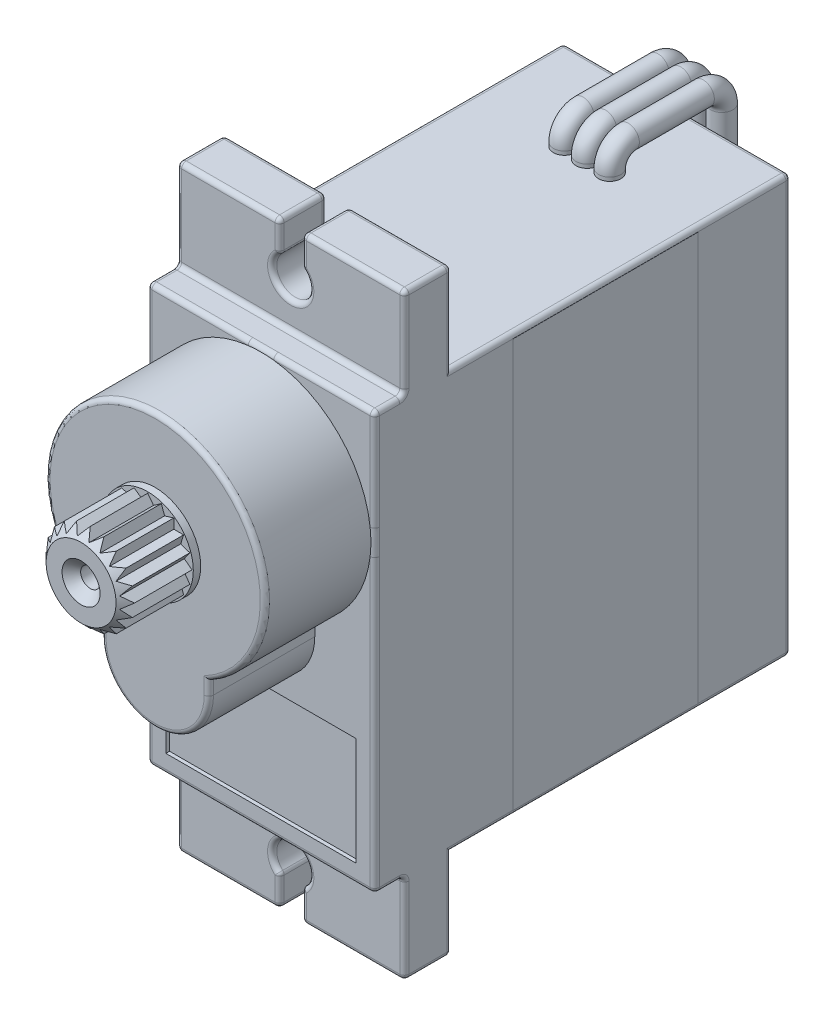
SolidWorks part; units mm, degrees
note: The reader was unsure of these and kept them because the rebuilt part matched: shared geometry of "Sketch1<3>", "Sketch3<3>", "Sketch8<3>".
ref_plane "Front Plane" through (0, 0, 0) normal (0, 0, 1) x (1, 0, 0)
ref_plane "Top Plane" through (0, 0, 0) normal (0, 1, 0) x (1, 0, 0)
ref_plane "Right Plane" through (0, 0, 0) normal (1, 0, 0) x (0, 0, -1)
sketch "Sketch1" plane through (0, 0, 0) normal (0, 0, 1) x (1, 0, 0)
  line L5 (-6.14, -16.41) -> (6.14, -16.41)
  line L6 (2.9, -5.93) -> (2.9, -5.1725)
  line L7 (-2.9, -5.93) -> (-2.9, -5.1725)
  line L8 (-6.14, -16.41) -> (-6.14, 6.14)
  line L9 (-6.14, 6.14) -> (6.14, 6.14)
  line L10 (6.14, -16.41) -> (6.14, 6.14)
  circle A0 centre (0, 0) radius 5.93
  arc A1 (-2.9, -5.93) -> (2.9, -5.93) centre (0, -5.93) ccw
  circle A2 centre (0, 0) radius 6.14 construction
  dimension "D3" = 11.86
  dimension "D4" = 5.8
  dimension "D6" = 12.28
  dimension "D7" = 22.55
ref_plane "Plane1" through (0, 0, -1.6) normal (0, 0, 1) x (1, 0, 0)
sketch "Sketch2" plane through (0, 0, -1.6) normal (0, 0, 1) x (1, 0, 0)
  line L1 (-6.14, 6.14) -> (6.14, 6.14)
  line L2 (-6.14, 6.14) -> (-6.14, 11)
  line L3 (-6.14, 11) -> (-0.6, 11)
  line L4 (6.14, 6.14) -> (6.14, 11)
  line L7 (0, 8.57) -> (0, 12.1069) construction
  line L8 (0.6, 9.37) -> (0.6, 11)
  line L9 (-0.6, 9.37) -> (-0.6, 11)
  line L10 (0.6, 11) -> (6.14, 11)
  line L11 (-0.6, 8.57) -> (-0.6, 12.1069) construction
  line L12 (0.6, 8.57) -> (0.6, 12.1069) construction
  line L13 (-6.14, -5.135) -> (6.14, -5.135) construction
  line L14 (0, -18.84) -> (0, -22.3769) construction
  line L15 (0.6, -21.27) -> (6.14, -21.27)
  line L16 (-0.6, -19.64) -> (-0.6, -21.27)
  line L17 (0.6, -19.64) -> (0.6, -21.27)
  line L18 (6.14, -16.41) -> (6.14, -21.27)
  line L19 (-6.14, -21.27) -> (-0.6, -21.27)
  line L20 (-6.14, -16.41) -> (-6.14, -21.27)
  line L21 (-6.14, -16.41) -> (6.14, -16.41)
  line L22 (-6.14, 6.14) -> (6.14, 6.14) construction
  line L23 (-6.14, -16.41) -> (-6.14, 6.14) construction
  line L24 (6.14, -16.41) -> (6.14, 6.14) construction
  arc A0 (-0.6, 9.37) -> (0.6, 9.37) centre (0, 8.57) ccw
  arc A1 (-0.6, -19.64) -> (0.6, -19.64) centre (0, -18.84) cw
  point P16 (6.14, 8.57)
  dimension "D2" = 0.6
  dimension "D4" = 2
  dimension "D1" = 4.86
  dimension "D3" = 0.6
extrude "Main Body" add sketch "Sketch1" against normal blind 22.46
extrude "Front Dial" add sketch "Sketch1<3>" along normal blind 5.72 contours L7 A1 L6 A0 | A0
sketch "Sketch1<3>" plane through (0, 0, 0) normal (0, 0, 1) x (1, 0, 0) same geometry as "Sketch1"
sketch "Sketch3" plane through (0, 0, 5.72) normal (0, 0, 1) x (1, 0, 0)
  line L0 (0, 0) -> (0, 2.39) construction
  line L1 (0, 0) -> (0.7386, 2.273) construction
  line L2 (0.7386, 2.273) -> (0.908, 1.782)
  line L3 (0.908, 1.782) -> (1.4048, 1.9336)
  line L4 (1.4048, 1.9336) -> (1.4142, 1.4142)
  line L5 (1.4142, 1.4142) -> (1.9336, 1.4048)
  line L6 (1.9336, 1.4048) -> (1.782, 0.908)
  line L7 (1.782, 0.908) -> (2.273, 0.7386)
  line L8 (2.273, 0.7386) -> (1.9754, 0.3129)
  line L9 (1.9754, 0.3129) -> (2.39, 0)
  line L10 (2.39, 0) -> (1.9754, -0.3129)
  line L11 (1.9754, -0.3129) -> (2.273, -0.7386)
  line L12 (2.273, -0.7386) -> (1.782, -0.908)
  line L13 (1.782, -0.908) -> (1.9336, -1.4048)
  line L14 (1.9336, -1.4048) -> (1.4142, -1.4142)
  line L15 (1.4142, -1.4142) -> (1.4048, -1.9336)
  line L16 (1.4048, -1.9336) -> (0.908, -1.782)
  line L17 (0.908, -1.782) -> (0.7386, -2.273)
  line L18 (0.7386, -2.273) -> (0.3129, -1.9754)
  line L19 (0.3129, -1.9754) -> (0, -2.39)
  line L20 (0.618, 1.9021) -> (0, 2) construction
  line L21 (0, 0) -> (0.3129, 1.9754) construction
  line L22 (0, 2.39) -> (0.3129, 1.9754)
  line L23 (0.3129, 1.9754) -> (0.7386, 2.273)
  line L24 (0, -2.39) -> (-0.3129, -1.9754)
  line L25 (0, 0) -> (-2.273, -0.7386) construction
  line L26 (0, 0) -> (-2.39, 0) construction
  line L27 (0, 0) -> (-2.273, 0.7386) construction
  line L28 (0, 0) -> (-1.9336, 1.4048) construction
  line L29 (0, 0) -> (-1.4048, 1.9336) construction
  line L30 (0, 0) -> (-0.7386, 2.273) construction
  line L31 (0, 0) -> (2.273, -0.7386) construction
  line L32 (0, 0) -> (1.9336, -1.4048) construction
  line L33 (0, 0) -> (1.4048, -1.9336) construction
  line L34 (0, 0) -> (0.7386, -2.273) construction
  line L35 (0, 0) -> (0, -2.39) construction
  line L36 (0, 0) -> (-0.7386, -2.273) construction
  line L37 (0, 0) -> (-1.4048, -1.9336) construction
  line L38 (0, 0) -> (-1.9336, -1.4048) construction
  line L39 (0, 0) -> (1.4048, 1.9336) construction
  line L40 (0, 0) -> (1.9336, 1.4048) construction
  line L41 (0, 0) -> (2.273, 0.7386) construction
  line L42 (0, 0) -> (2.39, 0) construction
  line L43 (-0.3129, -1.9754) -> (-0.7386, -2.273)
  line L44 (-0.7386, -2.273) -> (-0.908, -1.782)
  line L45 (-0.908, -1.782) -> (-1.4048, -1.9336)
  line L46 (-1.4048, -1.9336) -> (-1.4142, -1.4142)
  line L47 (-1.4142, -1.4142) -> (-1.9336, -1.4048)
  line L48 (-1.9336, -1.4048) -> (-1.782, -0.908)
  line L49 (-1.782, -0.908) -> (-2.273, -0.7386)
  line L50 (-2.273, -0.7386) -> (-1.9754, -0.3129)
  line L51 (-1.9754, -0.3129) -> (-2.39, 0)
  line L52 (-2.39, 0) -> (-1.9754, 0.3129)
  line L53 (-1.9754, 0.3129) -> (-2.273, 0.7386)
  line L54 (-2.273, 0.7386) -> (-1.782, 0.908)
  line L55 (-1.782, 0.908) -> (-1.9336, 1.4048)
  line L56 (-1.9336, 1.4048) -> (-1.4142, 1.4142)
  line L57 (-1.4142, 1.4142) -> (-1.4048, 1.9336)
  line L58 (-1.4048, 1.9336) -> (-0.908, 1.782)
  line L59 (-0.908, 1.782) -> (-0.7386, 2.273)
  line L60 (-0.7386, 2.273) -> (-0.3129, 1.9754)
  line L61 (-0.3129, 1.9754) -> (0, 2.39)
  circle A0 centre (0, 0) radius 2.46
  circle A1 centre (0, 0) radius 2.39 construction
  circle A2 centre (0, 0) radius 2 construction
  point P27 (0, 0)
  point P88 (0, 0)
  dimension "D1" = 4.92
  dimension "D2" = 4.78
  dimension "D3" = 4
  dimension "D4" = 20
  dimension "D5" = 20
extrude "Gear Base" add sketch "Sketch3" along normal blind 0.4 contours A0
extrude "Gear" add sketch "Sketch3<3>" along normal blind 4 contours L61 L60 L59 L58 L57 L56 L55 L54 L53 L52 L51 L50 L49 L48 L47 L46 L45 L44 L43 L24 L19 L18 L17 L16 L15 L14 L13 L12 L11 L10 L9 L8 L7 L6 L5 L4 L3 L2 L23 L22
sketch "Sketch3<3>" plane through (0, 0, 5.72) normal (0, 0, 1) x (1, 0, 0) same geometry as "Sketch3"
sketch "Sketch4" plane through (0, 0, 0) normal (0, 1, 0) x (1, 0, 0)
  line L0 (0, 0) -> (0, -15.1218) construction
  line L1 (0, -10.4175) -> (0, -6.12)
  line L2 (0, -6.12) -> (0.5, -6.12)
  line L3 (0.5, -6.12) -> (0.5221, -9.22)
  line L4 (0.3129, -9.72) -> (0.7386, -9.72) construction
  line L5 (1.0257, -9.72) -> (1.89, -9.72)
  line L6 (2.39, -9.22) -> (2.39, -7.8332)
  line L7 (2.39, -9.72) -> (2.39, -6.12) construction
  line L8 (2.39, -7.8332) -> (3.9331, -7.8332)
  line L9 (3.9331, -7.8332) -> (3.9331, -10.4175)
  line L10 (3.9331, -10.4175) -> (0, -10.4175)
  line L11 (0.5221, -9.22) -> (1.0257, -9.72)
  line L12 (1.89, -9.72) -> (2.39, -9.22)
  point P8 (0.5257, -9.72)
  point P11 (2.39, -9.72)
  dimension "D1" = 0.5
revolve "Gear Front" cut sketch "Sketch4" angle 360 about L0
extrude "Flange" add sketch "Sketch2" against normal blind 2.54
sketch "Sketch5" plane through (0, 0, -4.14) normal (0, 0, -1) x (-1, 0, 0)
  line L42 (-5.34, 6.14) -> (5.34, 6.14)
  line L43 (5.34, 6.14) -> (5.34, -16.41) construction
  line L45 (5.34, -5.135) -> (-0.3542, -5.135) construction
  line L46 (-5.34, -16.41) -> (-5.34, -20.47)
  line L47 (-5.34, -20.47) -> (-1.4, -20.47)
  line L48 (5.34, 10.2) -> (5.34, 6.14)
  line L49 (1.4, 10.2) -> (5.34, 10.2)
  line L50 (1.4, 9.7014) -> (1.4, 10.2)
  line L51 (-1.4, 10.2) -> (-1.4, 9.7014)
  line L52 (-5.34, 10.2) -> (-1.4, 10.2)
  line L53 (-5.34, 6.14) -> (-5.34, 10.2)
  line L54 (5.34, 10.2) -> (5.34, 6.14)
  line L55 (1.4, 10.2) -> (5.34, 10.2)
  line L56 (1.4, 9.7014) -> (1.4, 10.2)
  line L57 (-1.4, 10.2) -> (-1.4, 9.7014)
  line L58 (-5.34, 10.2) -> (-1.4, 10.2)
  line L59 (-5.34, 6.14) -> (-5.34, 10.2)
  line L60 (-1.4, -20.47) -> (-1.4, -19.9714)
  line L61 (1.4, -19.9714) -> (1.4, -20.47)
  line L62 (1.4, -20.47) -> (5.34, -20.47)
  line L63 (5.34, -20.47) -> (5.34, -16.41)
  line L64 (-5.34, -16.41) -> (5.34, -16.41)
  line L65 (-6.14, -16.41) -> (6.14, -16.41) construction
  arc A5 (-1.4, -19.9714) -> (1.4, -19.9714) centre (0, -18.84) cw
  arc A6 (-1.4, 9.7014) -> (1.4, 9.7014) centre (0, 8.57) ccw
  arc A7 (-1.4, 9.7014) -> (1.4, 9.7014) centre (0, 8.57) ccw
  dimension "D1" = 0.8
extrude "Flange Shell" cut sketch "Sketch5" against normal blind 1
fillet "Body Fillet" radius 0.25 62 edges at (0, 6.14, -22.46) (-2.9, -5.5513, 5.72) (-6.14, -5.135, -22.46) (0, -8.83, 5.72) (2.9, -5.5513, 5.72) (0, 5.93, 5.72) (6.14, 6.14, -0.8) (-6.14, 6.14, -0.8) (-6.14, 8.57, -4.14) (-3.37, 11, -4.14) (-6.14, 11, -2.87) (-0.6, 10.185, -4.14) (-0.6, 11, -2.87) (0, 7.57, -4.14) (-0.6, 9.37, -2.87) (0.6, 10.185, -4.14) (0.6, 9.37, -2.87) (3.37, 11, -4.14) (0.6, 11, -2.87) (6.14, 8.57, -4.14) (6.14, 11, -2.87) (-6.14, 8.57, -1.6) (0, 6.14, -1.6) (6.14, 8.57, -1.6) (3.37, 11, -1.6) (0.6, 10.185, -1.6) (0, 7.57, -1.6) (-0.6, 10.185, -1.6) (-3.37, 11, -1.6) (-6.14, -16.41, -0.8) (6.14, -16.41, -0.8) (0, -17.84, -4.14) (0.6, -19.64, -2.87) (-0.6, -20.455, -4.14) (-0.6, -19.64, -2.87) (-3.37, -21.27, -4.14) (-0.6, -21.27, -2.87) (-6.14, -18.84, -4.14) (-6.14, -21.27, -2.87) (6.14, -18.84, -4.14) (3.37, -21.27, -4.14) (6.14, -21.27, -2.87) (0.6, -20.455, -4.14) (0.6, -21.27, -2.87) (0, -17.84, -1.6) (0.6, -20.455, -1.6) (3.37, -21.27, -1.6) (6.14, -18.84, -1.6) (0, -16.41, -1.6) (-6.14, -18.84, -1.6) (-3.37, -21.27, -1.6) (-0.6, -20.455, -1.6) (0, -16.41, -22.46) (-6.14, -5.135, 0) (0, 6.14, 0) (6.14, -5.135, 0) (0, -16.41, 0) (-6.14, -16.41, -13.3) (-6.14, 6.14, -13.3) (6.14, 6.14, -13.3) (6.14, -16.41, -13.3) (6.14, -5.135, -22.46)
sketch "Sketch6" plane through (0, 0, 0) normal (0, 0, 1) x (1, 0, 0)
  line L3 (-3.3787, -8.83) -> (4.0232, -8.83) construction
  line L4 (-5.14, -9.58) -> (5.14, -9.58)
  line L5 (-3.3787, -9.58) -> (4.0232, -9.58) construction
  line L6 (-5.14, -0.6876) -> (-5.14, -15.41)
  line L7 (5.14, -15.41) -> (5.14, -0.6876)
  line L8 (-5.14, -15.41) -> (5.14, -15.41)
  line L9 (-5.14, -9.58) -> (-5.14, -15.41)
  line L10 (5.14, -15.41) -> (5.14, -9.58)
  line L11 (-5.14, -15.41) -> (5.14, -15.41)
  arc A0 (-2.9, -5.93) -> (2.9, -5.93) centre (0, -5.93) ccw construction
  dimension "D2" = 0.75
  dimension "D1" = 0.75
extrude "Front Face Divot" cut sketch "Sketch6" against normal blind 0.2
sketch "Sketch7" plane through (0, 0, -22.46) normal (0, 0, -1) x (-1, 0, 0)
  line L2 (-5.89, -16.16) -> (5.89, -16.16) construction
  line L3 (-5.89, 5.89) -> (-5.89, -16.16) construction
  line L4 (5.89, 5.89) -> (-5.89, 5.89) construction
  line L5 (5.89, -16.16) -> (5.89, 5.89) construction
  circle A0 centre (-4.765, 4.765) radius 0.875
  circle A1 centre (4.765, 4.765) radius 0.875
  circle A2 centre (4.765, -15.035) radius 0.875
  circle A3 centre (-4.765, -15.035) radius 0.875
  circle A4 centre (-4.765, -15.035) radius 1.125 construction
  circle A6 centre (4.765, 4.765) radius 1.125 construction
  dimension "D1" = 1.75
  dimension "D2" = 0.25
extrude "Screw Holes" cut sketch "Sketch7" against normal blind 1
sketch "Sketch8" plane through (0, 0, -21.46) normal (0, 0, -1) x (-1, 0, 0)
  line L0 (-5.54, 4.765) -> (-3.99, 4.765) construction
  line L1 (-4.765, 3.99) -> (-4.765, 5.54) construction
  line L2 (-5.5253, -15.185) -> (-4.915, -15.185)
  line L3 (-4.915, -14.2747) -> (-4.915, -14.885)
  line L4 (4.765, 5.54) -> (4.765, 3.99) construction
  line L5 (5.54, 4.765) -> (3.99, 4.765) construction
  line L6 (4.765, -15.81) -> (4.765, -14.26) construction
  line L7 (5.54, -15.035) -> (3.99, -15.035) construction
  line L8 (-5.54, -15.035) -> (-3.99, -15.035) construction
  line L9 (-4.765, -14.26) -> (-4.765, -15.81) construction
  line L10 (5.5253, -14.885) -> (4.915, -14.885)
  line L11 (4.915, -15.7953) -> (4.915, -15.185)
  line L12 (4.615, 5.5253) -> (4.615, 4.915)
  line L13 (5.5253, 4.915) -> (4.915, 4.915)
  line L14 (-5.5253, 4.615) -> (-4.915, 4.615)
  line L15 (-4.615, 4.0047) -> (-4.615, 4.615)
  line L16 (-5.5253, -14.885) -> (-4.915, -14.885)
  line L17 (-4.615, -14.2747) -> (-4.615, -14.885)
  line L18 (5.5253, -15.185) -> (4.915, -15.185)
  line L19 (4.615, -15.7953) -> (4.615, -15.185)
  line L20 (4.915, 5.5253) -> (4.915, 4.915)
  line L21 (5.5253, 4.615) -> (4.915, 4.615)
  line L22 (-5.5253, 4.915) -> (-4.915, 4.915)
  line L23 (-4.915, 4.0047) -> (-4.915, 4.615)
  line L24 (-4.615, -15.185) -> (-4.615, -15.7953)
  line L25 (-4.915, 3.99) -> (-4.915, 5.54) construction
  line L26 (-4.615, 3.99) -> (-4.615, 5.54) construction
  line L27 (-5.54, 4.615) -> (-3.99, 4.615) construction
  line L28 (-5.54, 4.915) -> (-3.99, 4.915) construction
  line L29 (4.615, 5.54) -> (4.615, 3.99) construction
  line L30 (4.915, 5.54) -> (4.915, 3.99) construction
  line L31 (5.54, 4.615) -> (3.99, 4.615) construction
  line L32 (5.54, 4.915) -> (3.99, 4.915) construction
  line L33 (5.54, -15.185) -> (3.99, -15.185) construction
  line L34 (5.54, -14.885) -> (3.99, -14.885) construction
  line L35 (4.615, -15.81) -> (4.615, -14.26) construction
  line L36 (4.915, -15.81) -> (4.915, -14.26) construction
  line L37 (-4.915, -14.26) -> (-4.915, -15.81) construction
  line L38 (-4.615, -14.26) -> (-4.615, -15.81) construction
  line L39 (-5.54, -15.185) -> (-3.99, -15.185) construction
  line L40 (-5.54, -14.885) -> (-3.99, -14.885) construction
  line L41 (-4.915, -15.185) -> (-4.915, -15.7953)
  line L42 (-4.615, -15.185) -> (-4.0047, -15.185)
  line L43 (-4.615, -14.885) -> (-4.0047, -14.885)
  line L44 (4.615, -14.885) -> (4.0047, -14.885)
  line L45 (4.615, -14.885) -> (4.615, -14.2747)
  line L46 (4.615, -15.185) -> (4.0047, -15.185)
  line L47 (4.915, -14.885) -> (4.915, -14.2747)
  line L48 (4.615, 4.915) -> (4.0047, 4.915)
  line L49 (4.915, 4.615) -> (4.915, 4.0047)
  line L50 (4.615, 4.615) -> (4.0047, 4.615)
  line L51 (4.615, 4.615) -> (4.615, 4.0047)
  line L52 (-4.615, 4.915) -> (-4.0047, 4.915)
  line L53 (-4.915, 4.915) -> (-4.915, 5.5253)
  line L54 (-4.615, 4.915) -> (-4.615, 5.5253)
  line L55 (-4.615, 4.615) -> (-4.0047, 4.615)
  circle A2 centre (-4.765, 4.765) radius 0.775
  circle A3 centre (-4.765, 4.765) radius 0.775
  circle A5 centre (4.765, 4.765) radius 0.775
  circle A6 centre (4.765, 4.765) radius 0.775
  circle A8 centre (-4.765, -15.035) radius 0.775
  circle A9 centre (-4.765, -15.035) radius 0.775
  circle A11 centre (4.765, -15.035) radius 0.775
  circle A12 centre (4.765, -15.035) radius 0.775
  dimension "D5" = 0.15
  dimension "D1" = 0.1
  dimension "D2" = 0.1
  dimension "D3" = 0.1
  dimension "D4" = 0.1
  dimension "D6" = 0.15
extrude "Screws" add sketch "Sketch8" along normal blind 1 contours L46 A12 L19 | L45 A12 L44 | L10 A12 L47 | L11 A12 L18 | L3 A9 L16 | L43 A9 L17 | L24 A9 L42 | L2 A9 L41 | L53 A3 L22 | L14 A3 L23 | L52 A3 L54 | L15 A3 L55 | L13 A6 L20 | L49 A6 L21 | L50 A6 L51 | L12 A6 L48
extrude "Screw Cross" add sketch "Sketch8<3>" along normal blind 0.7 contours L20 A6 L12 L48 L50 L51 L49 L21 L13 | L54 A3 L53 L22 L14 L23 L15 L55 L52 | L17 A9 L3 L16 L2 L41 L24 L42 L43 | L47 A12 L45 L44 L46 L19 L11 L18 L10
sketch "Sketch8<3>" plane through (0, 0, -21.46) normal (0, 0, -1) x (-1, 0, 0) same geometry as "Sketch8"
fillet "Screw Fillet" radius 0.1 16 edges at (-5.313, 5.313, -22.46) (-5.313, 4.217, -22.46) (-4.217, 4.217, -22.46) (-4.217, 5.313, -22.46) (5.313, 4.217, -22.46) (4.217, 4.217, -22.46) (4.217, 5.313, -22.46) (5.313, 5.313, -22.46) (4.217, -15.583, -22.46) (4.217, -14.487, -22.46) (5.313, -14.487, -22.46) (5.313, -15.583, -22.46) (-4.217, -15.583, -22.46) (-5.313, -15.583, -22.46) (-5.313, -14.487, -22.46) (-4.217, -14.487, -22.46)
sketch "Sketch10" plane through (0, 0, 0) normal (-1, 0, 0) x (0, 0, 1)
  line L0 (-3.89, 5.89) -> (-22.21, 5.89) construction
  line L1 (-17.46, 5.89) -> (-7.46, 5.89)
  line L2 (-17.46, 5.89) -> (-17.46, -16.16)
  line L3 (-17.46, -16.16) -> (-7.46, -16.16)
  line L4 (-7.46, 5.89) -> (-7.46, -16.16)
  line L5 (-22.21, -16.16) -> (-3.89, -16.16) construction
  line L6 (-22.46, -16.16) -> (-22.46, 5.89) construction
  dimension "D1" = 10
  dimension "D2" = 5
extrude "Sticker Base" add sketch "Sketch10" against normal offset from surface 0.01 and the other way offset from surface (6.24 mm away) 0.1 up to face at (6.14, -4.4903, -4.4552) offset beyond the face yes other way up to face at (-6.14, -4.4959, -4.4552)
sketch "Sketch12" plane through (0, 6.14, 0) normal (0, 1, 0) x (1, 0, 0)
  line L2 (-5.89, 18.21) -> (5.89, 18.21)
  line L3 (-5.89, 18.21) -> (5.89, 18.21) construction
  circle A0 centre (0, 17.61) radius 0.6
  circle A1 centre (1.22, 17.61) radius 0.6
  circle A2 centre (-1.22, 17.61) radius 0.6
  dimension "D2" = 1.2
  dimension "D3" = 1.22
  dimension "D4" = 1.22
  dimension "D1" = 4.25
sketch "Sketch13" plane through (0, 0, 0) normal (1, 0, 0) x (0, 0, -1)
  line L0 (17.61, 5.94) -> (17.61, 6.34)
  line L1 (18.61, 7.34) -> (22.66, 7.34)
  line L2 (4.14, 6.14) -> (22.21, 6.14) construction
  line L3 (23.66, 6.34) -> (23.66, 1.34)
  line L4 (22.46, 5.89) -> (22.46, -16.16) construction
  arc A0 (17.61, 6.34) -> (18.61, 7.34) centre (18.61, 6.34) cw
  arc A1 (22.66, 7.34) -> (23.66, 6.34) centre (22.66, 6.34) cw
  point P2 (17.61, 6.14)
  dimension "D1" = 1
  dimension "D2" = 1.2
  dimension "D3" = 1.2
  dimension "D5" = 5
sweep "Wires" add profiles "Sketch12" path "Sketch13"
sketch "Sketch14" plane through (0, 0, 0) normal (1, 0, 0) x (0, 0, -1)
  line L0 (23.06, 1.34) -> (24.26, 1.34) construction
  line L1 (23.06, 1.34) -> (24.26, 1.34)
  line L2 (24.26, 1.34) -> (23.06, 2.54)
  line L3 (23.06, 1.34) -> (23.06, 2.54)
  dimension "D1" = 45
extrude "Wire Trim" cut sketch "Sketch14" against normal through all both and the other way through all
sketch "Sketch15" plane through (0, 0, 5.72) normal (0, 0, 1) x (1, 0, 0)
  line L0 (0, 0) -> (0, -22.3652) construction
  line L1 (0, 0) -> (9.3138, -21.9313) construction
  line L2 (0, 0) -> (0, 20.2144) construction
  line L3 (0, 0) -> (8.7, 20.486) construction
  line L4 (7.377, -17.3708) -> (5.8135, -13.689)
  line L5 (5.8135, 13.689) -> (7.377, 17.3708)
  arc A0 (5.8135, -13.689) -> (7.377, -17.3708) centre (6.5953, -15.5299) ccw
  arc A1 (7.377, 17.3708) -> (5.8135, 13.689) centre (6.5953, 15.5299) ccw
  dimension "D3" = 2
  dimension "D1" = 23.01
  dimension "D2" = 23.01
  dimension "D4" = 16.8723
extrude "Alignment aid" [suppressed] add sketch "Sketch15" along normal blind 4 separate body
equation "\"D3@Sketch13\"=\"D2@Sketch13\""
equation "\"D4@Sketch12\"=\"D3@Sketch12\""
